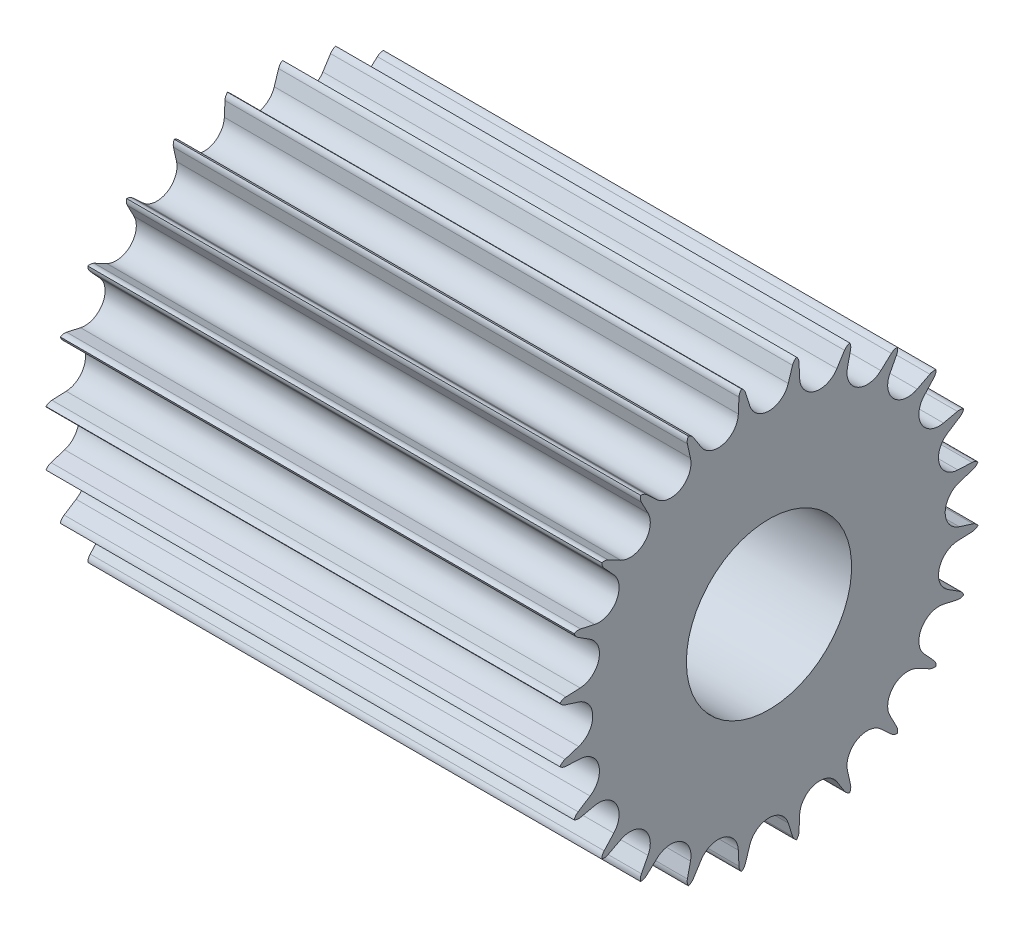
SolidWorks part; units mm, degrees
ref_plane "前视基准面" through (0, 0, 0) normal (0, 0, 1) x (1, 0, 0)
ref_plane "上视基准面" through (0, 0, 0) normal (0, 1, 0) x (1, 0, 0)
ref_plane "右视基准面" through (0, 0, 0) normal (1, 0, 0) x (0, 0, -1)
sketch "草图1" plane through (0, 0, 0) normal (0, 0, 1) x (1, 0, 0)
  line L0 (0, 0) -> (64.8368, 0) construction
  line L1 (0, 2.5) -> (0, 11.6)
  line L2 (0, 11.6) -> (28, 11.6)
  line L3 (28, 11.6) -> (28, 4.5)
  line L4 (28, 4.5) -> (20, 4.5)
  line L5 (20, 4.5) -> (20, 2.5)
  line L6 (20, 2.5) -> (0, 2.5)
  dimension "L" = 20
  dimension "B" = 28
  dimension "d" = 5
  dimension "d1" = 9
  dimension "da" = 23.2
revolve "旋转1" add sketch "草图1" angle 360 about L0
chamfer "倒角1" distance 1 angle 45 2 edges at (20, 0, 2.5) (0, 0, 2.5)
sketch "草图4" plane through (0, 0, 0) normal (-1, 0, 0) x (0, 0, 1)
  line L1 (-1, 2.2913) -> (1, 2.2913)
  line L2 (-1, 2.2913) -> (-1, 3.5)
  line L3 (-1, 3.5) -> (1, 3.5)
  line L4 (1, 2.2913) -> (1, 3.5)
  circle A0 centre (0, 0) radius 2.5 construction
  point P6 (0, 3.5)
  dimension "键槽高度" = 3.5
  dimension "键槽宽度" = 2
  dimension "t1" = 1
extrude "切除-拉伸1" cut sketch "草图4" against normal through all
sketch "草图6" plane through (0, 0, 0) normal (1, 0, 0) x (0, 0, -1)
  line L0 (0, 0) -> (0, 30.6512) construction
  line L1 (1.2827, 11.11) -> (1.0491, 10.3692)
  line L2 (2.3306, 11.3635) -> (2.8158, 12.9024)
  line L3 (-2.3306, 11.3635) -> (-2.8158, 12.9024)
  line L4 (-1.2827, 11.11) -> (-1.0491, 10.3692)
  circle A0 centre (0, 0) radius 11.6 construction
  circle A1 centre (0, 0) radius 9.6 construction
  arc A2 (-1.0491, 10.3692) -> (1.0491, 10.3692) centre (0, 10.7) ccw
  arc A3 (2.8158, 12.9024) -> (-2.8158, 12.9024) centre (0, 0) ccw
  arc A4 (1.2827, 11.11) -> (1.8388, 11.4533) centre (1.7595, 10.9597) cw
  arc A5 (1.8388, 11.4533) -> (2.3306, 11.3635) centre (0, 0) cw
  arc A6 (-1.8388, 11.4533) -> (-2.3306, 11.3635) centre (0, 0) ccw
  arc A7 (-1.2827, 11.11) -> (-1.8388, 11.4533) centre (-1.7595, 10.9597) ccw
  point P7 (0, 4.8294)
  point P8 (0, 28.6512)
  point P15 (1.41, 11.514)
  dimension "D1" = 19.2
  dimension "ra" = 0.5
  dimension "rf" = 1.1
  dimension "hg" = 2
  dimension "D3" = 0.5
  dimension "D4" = 1.6136
  dimension "angle" = 35
  dimension "bw" = 4.8294
extrude "切除-拉伸2" cut sketch "草图6" along normal up to next
ref_axis "基准轴1" through (-1.4, 0, 0) along (1, 0, 0)
pattern_circular "阵列(圆周)3" count 24 over 360 about axis through (-1.4, 0, 0) along (1, 0, 0) of "切除-拉伸2"
equation "\"键槽高度@草图4\" = \"d@草图1\" / 2  + \"t1@草图4\""
equation "\"D1@草图6\" = \"da@草图1\"  - \"hg@草图6\" - \"hg@草图6\""
equation "\"D3@草图6\" = \"ra@草图6\""
